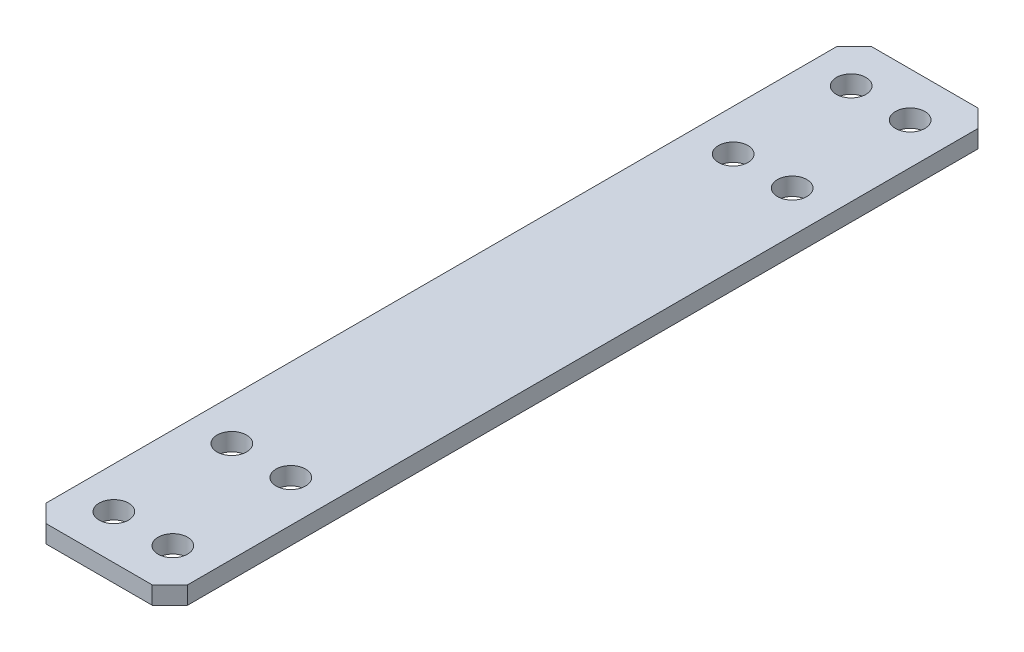
SolidWorks part; units mm, degrees
ref_plane "前基準面" through (0, 0, 0) normal (0, 0, 1) x (1, 0, 0)
ref_plane "上基準面" through (0, 0, 0) normal (0, 1, 0) x (1, 0, 0)
ref_plane "右基準面" through (0, 0, 0) normal (1, 0, 0) x (0, 0, -1)
sketch "草圖1" plane through (0, 0, 0) normal (0, 1, 0) x (1, 0, 0)
  line L1 (-12, 70) -> (12, 70)
  line L2 (-12, 70) -> (-12, -70)
  line L3 (-12, -70) -> (12, -70)
  line L4 (12, 70) -> (12, -70)
  line L5 (-12, 70) -> (12, -70) construction
  line L6 (-12, -70) -> (12, 70) construction
  point P0 (0, 0)
  point P6 (5, 62.5)
  point P7 (5, -62.5)
  point P8 (-5, 42.5)
  point P11 (-5, -62.5)
  dimension "D1" = 140
  dimension "D2" = 24
  dimension "D3" = 125
  dimension "D4" = 7.5
  dimension "D5" = 7
  dimension "D6" = 10
  dimension "D7" = 105
extrude "填料-伸長1" add sketch "草圖1" along normal blind 3
sketch "草圖2" plane through (0, 3, 0) normal (0, 1, 0) x (1, 0, 0)
  line L0 (5, 62.5) -> (-5, 62.5) construction
  line L1 (5, 62.5) -> (5, -42.5) construction
  point P0 (5, 62.5)
  point P1 (-5, 42.5)
  point P3 (5, -62.5)
  point P5 (-5, -62.5)
  point P9 (5, 42.5)
  point P11 (-5, 62.5)
  point P12 (-5, -42.5)
  point P13 (5, -42.5)
  dimension "D3" = 10
  dimension "D4" = 105
  dimension "D1" = 2
  dimension "D2" = 2
hole_wizard "Ø5.0 (5) 直徑孔1" positions "3D草圖1" profile "草圖3" hole size "Ø5.0" standard "GB" end condition through all
sketch3d "3D草圖1"
  point P0 (-5, 3, -62.5)
  point P3 (5, 3, -62.5)
  point P6 (5, 3, -42.5)
  point P9 (-5, 3, -42.5)
  point P12 (5, 3, 42.5)
  point P15 (-5, 3, 42.5)
  point P18 (5, 3, 62.5)
  point P21 (-5, 3, 62.5)
sketch "草圖3" plane through (-5, 3, -62.5) normal (1, 0, 0) x (0, 0, 1)
  line L0 (0, 0) -> (0, 3)
  line L1 (0, 3) -> (2.5, 3)
  line L2 (2.5, 3) -> (2.5, 0)
  line L5 (2.5, 0) -> (0, 0)
  line L11 (0, -6.35) -> (0, 107.95) construction
  dimension "貫穿孔直徑" = 5
  dimension "貫穿孔深度" = 3
chamfer "導角1" distance 3 angle 45 4 edges at (-12, 1.5, 70) (12, 1.5, 70) (12, 1.5, -70) (-12, 1.5, -70)
